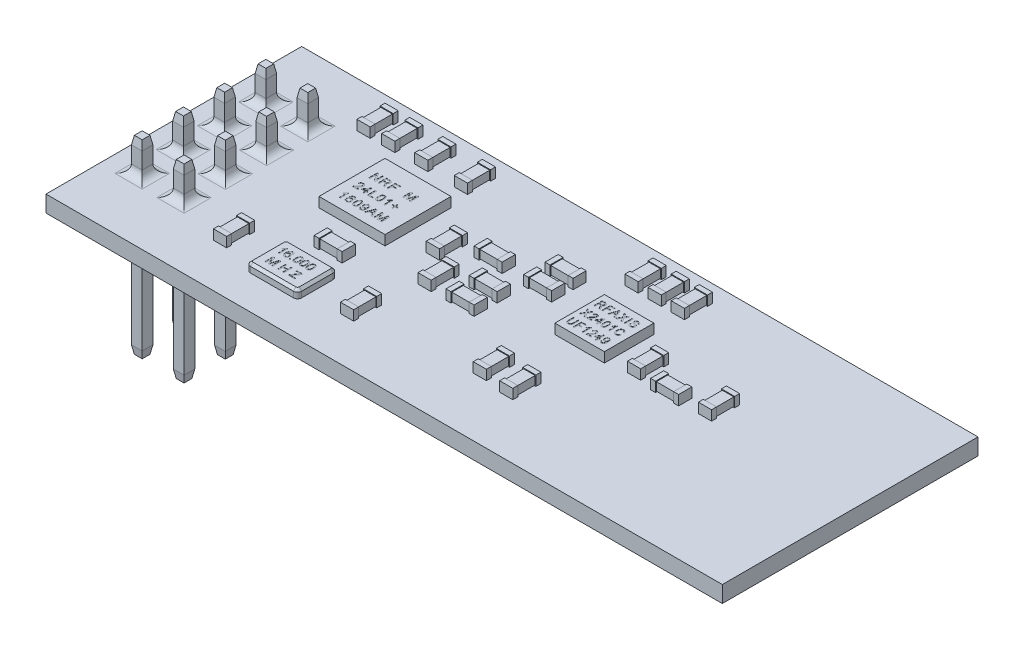
SolidWorks part; units mm, degrees
ref_plane "Спереди" through (0, 0, 0) normal (0, 0, 1) x (1, 0, 0)
ref_plane "Сверху" through (0, 0, 0) normal (0, 1, 0) x (1, 0, 0)
ref_plane "Справа" through (0, 0, 0) normal (1, 0, 0) x (0, 0, -1)
sketch "Эскиз1" plane through (0, 0, 0) normal (0, 1, 0) x (1, 0, 0)
  line L1 (0, -7.75) -> (41, -7.75)
  line L2 (0, -7.75) -> (0, 7.75)
  line L3 (0, 7.75) -> (41, 7.75)
  line L4 (41, -7.75) -> (41, 7.75)
  dimension "D1" = 41
  dimension "D2" = 15.5
extrude "Бобышка-Вытянуть1" add sketch "Эскиз1" along normal blind 1
sketch "Эскиз2" plane through (0, 0, 0) normal (0, -1, 0) x (1, 0, 0)
  line L0 (0, 0) -> (0.6, 0) construction
  line L1 (0, -7.75) -> (0, 7.75) construction
  line L2 (0.6, 4.5) -> (0.6, 3)
  line L3 (0.6, 3) -> (1.1, 2.5)
  line L4 (1.1, 2.5) -> (0.6, 2)
  line L5 (0.6, 2) -> (0.6, 0.5)
  line L6 (0.6, 0.5) -> (1.1, 0)
  line L7 (1.1, 0) -> (0.6, -0.5)
  line L8 (0.6, -0.5) -> (0.6, -2)
  line L9 (0.6, -2) -> (1.1, -2.5)
  line L10 (1.1, -2.5) -> (0.6, -3)
  line L11 (0.6, -3) -> (0.6, -4.5)
  line L12 (0.6, -4.5) -> (1.1, -5)
  line L13 (1.1, -5) -> (5.1, -5)
  line L14 (5.1, -5) -> (5.6, -4.5)
  line L15 (5.6, -4.5) -> (5.6, -3)
  line L16 (5.6, -3) -> (5.1, -2.5)
  line L17 (5.1, -2.5) -> (5.6, -2)
  line L18 (5.6, -2) -> (5.6, -0.5)
  line L19 (5.6, -0.5) -> (5.1, 0)
  line L20 (5.1, 0) -> (5.6, 0.5)
  line L21 (5.6, 0.5) -> (5.6, 2)
  line L22 (5.6, 2) -> (5.1, 2.5)
  line L23 (5.1, 2.5) -> (5.6, 3)
  line L24 (5.6, 3) -> (5.6, 4.5)
  line L25 (5.6, 4.5) -> (5.1, 5)
  line L26 (5.1, 5) -> (1.1, 5)
  line L27 (1.1, 5) -> (0.6, 4.5)
  line L28 (0.6, 0.5) -> (0.6, -0.5) construction
  line L29 (1.1, 2.5) -> (5.1, 2.5) construction
  line L30 (1.1, 0) -> (5.1, 0) construction
  line L31 (1.1, -2.5) -> (5.1, -2.5) construction
  dimension "D1" = 5
  dimension "D2" = 10
  dimension "D3" = 0.5
  dimension "D4" = 0.6
extrude "Бобышка-Вытянуть2" add sketch "Эскиз2" along normal blind 2.5
sketch "Эскиз3" plane through (0, -2.5, 0) normal (0, -1, 0) x (1, 0, 0)
  line L0 (3.1, 5) -> (3.1, -5) construction
  line L1 (5.1, 5) -> (1.1, 5) construction
  line L2 (1.1, -5) -> (5.1, -5) construction
  line L3 (1.83, 3.75) -> (4.37, 3.75) construction
  line L4 (0.6, 3.75) -> (1.83, 3.75) construction
  line L5 (0.6, 4.5) -> (0.6, 3) construction
  line L6 (0.6, 1.25) -> (1.83, 1.25) construction
  line L7 (0.6, 2) -> (0.6, 0.5) construction
  line L8 (1.83, 1.25) -> (4.37, 1.25) construction
  line L9 (4.37, 1.25) -> (4.37, 3.75) construction
  line L10 (1.83, 3.75) -> (1.83, 1.25) construction
  line L11 (0.6, -1.25) -> (1.83, -1.25) construction
  line L12 (0.6, -0.5) -> (0.6, -2) construction
  line L13 (1.83, -1.25) -> (1.83, 1.25) construction
  line L14 (1.83, -1.25) -> (4.37, -1.25) construction
  line L15 (4.37, -1.25) -> (4.37, 1.25) construction
  line L16 (0.6, -3.75) -> (1.83, -3.75) construction
  line L17 (0.6, -3) -> (0.6, -4.5) construction
  line L18 (1.83, -3.75) -> (1.83, -1.25) construction
  line L19 (1.83, -3.75) -> (4.37, -3.75) construction
  line L20 (4.37, -3.75) -> (4.37, -1.25) construction
  line L21 (1.505, 4.075) -> (2.155, 3.425) construction
  line L22 (1.505, 3.425) -> (2.155, 3.425)
  line L23 (1.505, 3.425) -> (1.505, 4.075)
  line L24 (1.505, 4.075) -> (2.155, 4.075)
  line L25 (2.155, 3.425) -> (2.155, 4.075)
  line L26 (4.045, 3.425) -> (4.695, 3.425)
  line L27 (4.045, 3.425) -> (4.045, 4.075)
  line L28 (4.045, 4.075) -> (4.695, 4.075)
  line L29 (4.695, 3.425) -> (4.695, 4.075)
  line L30 (1.505, 0.925) -> (2.155, 0.925)
  line L31 (1.505, 0.925) -> (1.505, 1.575)
  line L32 (1.505, 1.575) -> (2.155, 1.575)
  line L33 (2.155, 0.925) -> (2.155, 1.575)
  line L34 (4.045, 0.925) -> (4.695, 0.925)
  line L35 (4.045, 0.925) -> (4.045, 1.575)
  line L36 (4.045, 1.575) -> (4.695, 1.575)
  line L37 (4.695, 0.925) -> (4.695, 1.575)
  line L38 (1.505, -1.575) -> (2.155, -1.575)
  line L39 (1.505, -1.575) -> (1.505, -0.925)
  line L40 (1.505, -0.925) -> (2.155, -0.925)
  line L41 (2.155, -1.575) -> (2.155, -0.925)
  line L42 (4.045, -1.575) -> (4.695, -1.575)
  line L43 (4.045, -1.575) -> (4.045, -0.925)
  line L44 (4.045, -0.925) -> (4.695, -0.925)
  line L45 (4.695, -1.575) -> (4.695, -0.925)
  line L46 (1.505, -4.075) -> (2.155, -4.075)
  line L47 (1.505, -4.075) -> (1.505, -3.425)
  line L48 (1.505, -3.425) -> (2.155, -3.425)
  line L49 (2.155, -4.075) -> (2.155, -3.425)
  line L50 (4.045, -4.075) -> (4.695, -4.075)
  line L51 (4.045, -4.075) -> (4.045, -3.425)
  line L52 (4.045, -3.425) -> (4.695, -3.425)
  line L53 (4.695, -4.075) -> (4.695, -3.425)
  line L54 (4.045, 4.075) -> (4.695, 3.425) construction
  line L55 (1.505, 1.575) -> (2.155, 0.925) construction
  line L56 (4.045, 1.575) -> (4.695, 0.925) construction
  line L57 (1.505, -0.925) -> (2.155, -1.575) construction
  line L58 (4.045, -0.925) -> (4.695, -1.575) construction
  line L59 (1.505, -3.425) -> (2.155, -4.075) construction
  line L60 (4.045, -3.425) -> (4.695, -4.075) construction
  point P8 (3.1, 3.75)
  dimension "D1" = 2.54
  dimension "D2" = 0.65
extrude "Бобышка-Вытянуть3" add sketch "Эскиз3" along normal blind 6
sketch "Эскиз8" plane through (0, 1, 0) normal (0, 1, 0) x (1, 0, 0)
  line L0 (2.155, -3.425) -> (2.155, -4.075) construction
  line L1 (1.505, 3.425) -> (2.155, 3.425)
  line L2 (1.505, 3.425) -> (1.505, 4.075)
  line L3 (1.505, 4.075) -> (2.155, 4.075)
  line L4 (2.155, 3.425) -> (2.155, 4.075)
  line L5 (4.045, 3.425) -> (4.695, 3.425)
  line L6 (4.045, 3.425) -> (4.045, 4.075)
  line L7 (4.045, 4.075) -> (4.695, 4.075)
  line L8 (4.695, 3.425) -> (4.695, 4.075)
  line L9 (1.505, 0.925) -> (2.155, 0.925)
  line L10 (1.505, 0.925) -> (1.505, 1.575)
  line L11 (1.505, 1.575) -> (2.155, 1.575)
  line L12 (2.155, 0.925) -> (2.155, 1.575)
  line L13 (4.045, 0.925) -> (4.695, 0.925)
  line L14 (4.045, 0.925) -> (4.045, 1.575)
  line L15 (4.045, 1.575) -> (4.695, 1.575)
  line L16 (4.695, 0.925) -> (4.695, 1.575)
  line L17 (1.505, -1.575) -> (2.155, -1.575)
  line L18 (1.505, -1.575) -> (1.505, -0.925)
  line L19 (1.505, -0.925) -> (2.155, -0.925)
  line L20 (2.155, -1.575) -> (2.155, -0.925)
  line L21 (4.045, -1.575) -> (4.695, -1.575)
  line L22 (4.045, -1.575) -> (4.045, -0.925)
  line L23 (4.045, -0.925) -> (4.695, -0.925)
  line L24 (4.695, -1.575) -> (4.695, -0.925)
  line L25 (1.505, -4.075) -> (2.155, -4.075)
  line L26 (1.505, -4.075) -> (1.505, -3.425)
  line L27 (1.505, -3.425) -> (2.155, -3.425)
  line L28 (2.155, -4.075) -> (2.155, -3.425)
  line L30 (4.045, -4.075) -> (4.695, -4.075)
  line L31 (4.045, -4.075) -> (4.045, -3.425)
  line L32 (4.045, -3.425) -> (4.695, -3.425)
  line L33 (4.695, -4.075) -> (4.695, -3.425)
extrude "Бобышка-Вытянуть5" add sketch "Эскиз8" along normal blind 2
chamfer "Фаска1" distance 0.5 angle 10 64 edges at (4.37, -8.5, -4.075) (4.695, -8.5, -3.75) (4.37, -8.5, -3.425) (4.045, -8.5, -3.75) (2.155, -8.5, -3.75) (1.83, -8.5, -4.075) (1.505, -8.5, -3.75) (1.83, -8.5, -3.425) (4.37, -8.5, -1.575) (4.695, -8.5, -1.25) (4.37, -8.5, -0.925) (4.045, -8.5, -1.25) (2.155, -8.5, -1.25) (1.83, -8.5, -1.575) (1.505, -8.5, -1.25) (1.83, -8.5, -0.925) (4.37, -8.5, 0.925) (4.695, -8.5, 1.25) (4.37, -8.5, 1.575) (4.045, -8.5, 1.25) (2.155, -8.5, 1.25) (1.83, -8.5, 0.925) (1.505, -8.5, 1.25) (1.83, -8.5, 1.575) (4.37, -8.5, 3.425) (4.695, -8.5, 3.75) (4.37, -8.5, 4.075) (4.045, -8.5, 3.75) (2.155, -8.5, 3.75) (1.83, -8.5, 4.075) (1.505, -8.5, 3.75) (1.83, -8.5, 3.425) (4.695, 3, -3.75) (4.37, 3, -4.075) (4.045, 3, -3.75) (4.37, 3, -3.425) (2.155, 3, -3.75) (1.83, 3, -4.075) (1.505, 3, -3.75) (1.83, 3, -3.425) (4.695, 3, -1.25) (4.37, 3, -1.575) (4.045, 3, -1.25) (4.37, 3, -0.925) (2.155, 3, -1.25) (1.83, 3, -1.575) (1.505, 3, -1.25) (1.83, 3, -0.925) (4.695, 3, 1.25) (4.37, 3, 0.925) (4.045, 3, 1.25) (4.37, 3, 1.575) (2.155, 3, 1.25) (1.83, 3, 0.925) (1.505, 3, 1.25) (1.83, 3, 1.575) (4.695, 3, 3.75) (4.37, 3, 3.425) (4.045, 3, 3.75) (4.37, 3, 4.075) (2.155, 3, 3.75) (1.83, 3, 3.425) (1.505, 3, 3.75) (1.83, 3, 4.075)
fillet "Скругление1" radius 0.5 32 edges at (1.83, 1, 3.425) (1.505, 1, 3.75) (2.155, 1, 3.75) (1.83, 1, 4.075) (4.695, 1, -3.75) (4.37, 1, -4.075) (4.045, 1, -3.75) (4.37, 1, -3.425) (2.155, 1, -3.75) (1.83, 1, -4.075) (1.505, 1, -3.75) (1.83, 1, -3.425) (4.695, 1, -1.25) (4.37, 1, -1.575) (4.045, 1, -1.25) (4.37, 1, -0.925) (2.155, 1, -1.25) (1.83, 1, -1.575) (1.505, 1, -1.25) (1.83, 1, -0.925) (2.155, 1, 1.25) (1.83, 1, 0.925) (1.505, 1, 1.25) (1.83, 1, 1.575) (4.695, 1, 1.25) (4.37, 1, 0.925) (4.045, 1, 1.25) (4.37, 1, 1.575) (4.695, 1, 3.75) (4.37, 1, 3.425) (4.045, 1, 3.75) (4.37, 1, 4.075)
sketch "Эскиз9" plane through (0, 1, 0) normal (0, 1, 0) x (1, 0, 0)
  line L0 (6.5, 6.4) -> (6.5, 5.3) construction
  line L1 (6.1, 6.4) -> (6.9, 6.4)
  line L2 (6.1, 6.4) -> (6.1, 6.7)
  line L3 (6.1, 6.7) -> (6.9, 6.7)
  line L4 (6.9, 6.4) -> (6.9, 6.7)
  line L5 (7.6, 6.4) -> (8.4, 6.4)
  line L6 (7.6, 6.4) -> (7.6, 6.7)
  line L7 (7.6, 6.7) -> (8.4, 6.7)
  line L8 (8.4, 6.4) -> (8.4, 6.7)
  line L9 (9.6, 6.4) -> (10.4, 6.4)
  line L10 (9.6, 6.4) -> (9.6, 6.7)
  line L11 (9.6, 6.7) -> (10.4, 6.7)
  line L12 (10.4, 6.4) -> (10.4, 6.7)
  line L13 (12, 6.4) -> (12.8, 6.4)
  line L14 (12, 6.4) -> (12, 6.7)
  line L15 (12, 6.7) -> (12.8, 6.7)
  line L16 (12.8, 6.4) -> (12.8, 6.7)
  line L17 (8, 6.4) -> (8, 5.3) construction
  line L18 (10, 6.4) -> (10, 5.3) construction
  line L19 (12.4, 6.4) -> (12.4, 5.3) construction
  line L20 (7.9, -3.7) -> (7.9, -4.8) construction
  line L21 (6.1, 5) -> (6.9, 5)
  line L22 (6.1, 5) -> (6.1, 5.3)
  line L23 (6.1, 5.3) -> (6.9, 5.3)
  line L24 (6.9, 5) -> (6.9, 5.3)
  line L25 (7.6, 5) -> (8.4, 5)
  line L26 (7.6, 5) -> (7.6, 5.3)
  line L27 (7.6, 5.3) -> (8.4, 5.3)
  line L28 (8.4, 5) -> (8.4, 5.3)
  line L29 (9.6, 5) -> (10.4, 5)
  line L30 (9.6, 5) -> (9.6, 5.3)
  line L31 (9.6, 5.3) -> (10.4, 5.3)
  line L32 (10.4, 5) -> (10.4, 5.3)
  line L33 (12, 5) -> (12.8, 5)
  line L34 (12, 5) -> (12, 5.3)
  line L35 (12, 5.3) -> (12.8, 5.3)
  line L36 (12.8, 5) -> (12.8, 5.3)
  line L37 (7.5, -3.7) -> (8.3, -3.7)
  line L38 (7.5, -3.7) -> (7.5, -3.4)
  line L39 (7.5, -3.4) -> (8.3, -3.4)
  line L40 (8.3, -3.7) -> (8.3, -3.4)
  line L41 (7.5, -5.1) -> (8.3, -5.1)
  line L42 (7.5, -5.1) -> (7.5, -4.8)
  line L43 (7.5, -4.8) -> (8.3, -4.8)
  line L44 (8.3, -5.1) -> (8.3, -4.8)
  line L45 (22.75, 6.4) -> (22.75, 5.3) construction
  line L46 (22.35, 6.7) -> (23.15, 6.7)
  line L47 (22.35, 6.7) -> (22.35, 6.4)
  line L48 (22.35, 6.4) -> (23.15, 6.4)
  line L49 (23.15, 6.7) -> (23.15, 6.4)
  line L50 (23.75, 6.7) -> (24.55, 6.7)
  line L51 (23.75, 6.7) -> (23.75, 6.4)
  line L52 (23.75, 6.4) -> (24.55, 6.4)
  line L53 (24.55, 6.7) -> (24.55, 6.4)
  line L54 (25.15, 6.7) -> (25.95, 6.7)
  line L55 (25.15, 6.7) -> (25.15, 6.4)
  line L56 (25.15, 6.4) -> (25.95, 6.4)
  line L57 (25.95, 6.7) -> (25.95, 6.4)
  line L58 (22.35, 5) -> (23.15, 5)
  line L59 (22.35, 5) -> (22.35, 5.3)
  line L60 (22.35, 5.3) -> (23.15, 5.3)
  line L61 (23.15, 5) -> (23.15, 5.3)
  line L62 (23.75, 5) -> (24.55, 5)
  line L63 (23.75, 5) -> (23.75, 5.3)
  line L64 (23.75, 5.3) -> (24.55, 5.3)
  line L65 (24.55, 5) -> (24.55, 5.3)
  line L66 (25.15, 5) -> (25.95, 5)
  line L67 (25.15, 5) -> (25.15, 5.3)
  line L68 (25.15, 5.3) -> (25.95, 5.3)
  line L69 (25.95, 5) -> (25.95, 5.3)
  line L70 (24.15, 6.4) -> (24.15, 5.3) construction
  line L71 (25.55, 6.4) -> (25.55, 5.3) construction
  line L72 (11.2, -2) -> (12.3, -2) construction
  line L73 (10.9, -2.4) -> (11.2, -2.4)
  line L74 (10.9, -2.4) -> (10.9, -1.6)
  line L75 (10.9, -1.6) -> (11.2, -1.6)
  line L76 (11.2, -2.4) -> (11.2, -1.6)
  line L77 (12.3, -2.4) -> (12.6, -2.4)
  line L78 (12.3, -2.4) -> (12.3, -1.6)
  line L79 (12.3, -1.6) -> (12.6, -1.6)
  line L80 (12.6, -2.4) -> (12.6, -1.6)
  line L81 (15.6, -3.7) -> (15.6, -4.8) construction
  line L82 (15.2, -3.4) -> (16, -3.4)
  line L83 (15.2, -3.4) -> (15.2, -3.7)
  line L84 (15.2, -3.7) -> (16, -3.7)
  line L85 (16, -3.4) -> (16, -3.7)
  line L86 (15.2, -5.1) -> (16, -5.1)
  line L87 (15.2, -5.1) -> (15.2, -4.8)
  line L88 (15.2, -4.8) -> (16, -4.8)
  line L89 (16, -5.1) -> (16, -4.8)
  line L90 (27.4, 1.9) -> (27.4, 0.8) construction
  line L91 (27, 1.9) -> (27.8, 1.9)
  line L92 (27, 1.9) -> (27, 2.2)
  line L93 (27, 2.2) -> (27.8, 2.2)
  line L94 (27.8, 1.9) -> (27.8, 2.2)
  line L95 (27, 0.5) -> (27.8, 0.5)
  line L96 (27, 0.5) -> (27, 0.8)
  line L97 (27, 0.8) -> (27.8, 0.8)
  line L98 (27.8, 0.5) -> (27.8, 0.8)
  line L99 (31.7, 1.9) -> (31.7, 0.8) construction
  line L100 (31.3, 2.2) -> (32.1, 2.2)
  line L101 (31.3, 2.2) -> (31.3, 1.9)
  line L102 (31.3, 1.9) -> (32.1, 1.9)
  line L103 (32.1, 2.2) -> (32.1, 1.9)
  line L104 (31.3, 0.5) -> (32.1, 0.5)
  line L105 (31.3, 0.5) -> (31.3, 0.8)
  line L106 (31.3, 0.8) -> (32.1, 0.8)
  line L107 (32.1, 0.5) -> (32.1, 0.8)
  line L108 (28.9, 0.7) -> (30, 0.7) construction
  line L109 (28.6, 0.3) -> (28.9, 0.3)
  line L110 (28.6, 0.3) -> (28.6, 1.1)
  line L111 (28.6, 1.1) -> (28.9, 1.1)
  line L112 (28.9, 0.3) -> (28.9, 1.1)
  line L113 (30, 0.3) -> (30.3, 0.3)
  line L114 (30, 0.3) -> (30, 1.1)
  line L115 (30, 1.1) -> (30.3, 1.1)
  line L116 (30.3, 0.3) -> (30.3, 1.1)
  line L117 (22.75, -2.8) -> (22.75, -3.9) construction
  line L118 (22.35, -2.8) -> (23.15, -2.8)
  line L119 (22.35, -2.8) -> (22.35, -2.5)
  line L120 (22.35, -2.5) -> (23.15, -2.5)
  line L121 (23.15, -2.8) -> (23.15, -2.5)
  line L122 (22.35, -4.2) -> (23.15, -4.2)
  line L123 (22.35, -4.2) -> (22.35, -3.9)
  line L124 (22.35, -3.9) -> (23.15, -3.9)
  line L125 (23.15, -4.2) -> (23.15, -3.9)
  line L126 (24.55, -3) -> (24.55, -4.1) construction
  line L127 (24.15, -3) -> (24.95, -3)
  line L128 (24.15, -3) -> (24.15, -2.7)
  line L129 (24.15, -2.7) -> (24.95, -2.7)
  line L130 (24.95, -3) -> (24.95, -2.7)
  line L131 (24.15, -4.4) -> (24.95, -4.4)
  line L132 (24.15, -4.4) -> (24.15, -4.1)
  line L133 (24.15, -4.1) -> (24.95, -4.1)
  line L134 (24.95, -4.4) -> (24.95, -4.1)
  line L135 (16.4, 0.2) -> (16.4, -0.9) construction
  line L136 (16, -1.2) -> (16.8, -1.2)
  line L137 (16, -1.2) -> (16, -0.9)
  line L138 (16, -0.9) -> (16.8, -0.9)
  line L139 (16.8, -1.2) -> (16.8, -0.9)
  line L140 (16, 0.2) -> (16.8, 0.2)
  line L141 (16, 0.2) -> (16, 0.5)
  line L142 (16, 0.5) -> (16.8, 0.5)
  line L143 (16.8, 0.2) -> (16.8, 0.5)
  line L144 (15, 2.1) -> (15, 1) construction
  line L145 (14.6, 0.7) -> (15.4, 0.7)
  line L146 (14.6, 0.7) -> (14.6, 1)
  line L147 (14.6, 1) -> (15.4, 1)
  line L148 (15.4, 0.7) -> (15.4, 1)
  line L149 (14.6, 2.1) -> (15.4, 2.1)
  line L150 (14.6, 2.1) -> (14.6, 2.4)
  line L151 (14.6, 2.4) -> (15.4, 2.4)
  line L152 (15.4, 2.1) -> (15.4, 2.4)
  line L153 (16.6, 2.3) -> (17.7, 2.3) construction
  line L154 (16.3, 1.9) -> (16.6, 1.9)
  line L155 (16.3, 1.9) -> (16.3, 2.7)
  line L156 (16.3, 2.7) -> (16.6, 2.7)
  line L157 (16.6, 1.9) -> (16.6, 2.7)
  line L158 (17.7, 1.9) -> (18, 1.9)
  line L159 (17.7, 1.9) -> (17.7, 2.7)
  line L160 (17.7, 2.7) -> (18, 2.7)
  line L161 (18, 1.9) -> (18, 2.7)
  line L162 (19.3, 1.9) -> (19.6, 1.9)
  line L163 (19.3, 1.9) -> (19.3, 2.7)
  line L164 (19.3, 2.7) -> (19.6, 2.7)
  line L165 (19.6, 1.9) -> (19.6, 2.7)
  line L166 (20.7, 1.9) -> (21, 1.9)
  line L167 (20.7, 1.9) -> (20.7, 2.7)
  line L168 (20.7, 2.7) -> (21, 2.7)
  line L169 (21, 1.9) -> (21, 2.7)
  line L170 (19.3, 3.2) -> (19.6, 3.2)
  line L171 (19.3, 3.2) -> (19.3, 4)
  line L172 (19.3, 4) -> (19.6, 4)
  line L173 (19.6, 3.2) -> (19.6, 4)
  line L174 (20.7, 3.2) -> (21, 3.2)
  line L175 (20.7, 3.2) -> (20.7, 4)
  line L176 (20.7, 4) -> (21, 4)
  line L177 (21, 3.2) -> (21, 4)
  line L178 (19.6, 2.3) -> (20.7, 2.3) construction
  line L179 (19.6, 3.6) -> (20.7, 3.6) construction
  line L180 (18, 0.6) -> (19.1, 0.6) construction
  line L181 (17.7, -1.2) -> (18, -1.2)
  line L182 (17.7, -1.2) -> (17.7, -0.4)
  line L183 (17.7, -0.4) -> (18, -0.4)
  line L184 (18, -1.2) -> (18, -0.4)
  line L185 (19.1, -1.2) -> (19.4, -1.2)
  line L186 (19.1, -1.2) -> (19.1, -0.4)
  line L187 (19.1, -0.4) -> (19.4, -0.4)
  line L188 (19.4, -1.2) -> (19.4, -0.4)
  line L189 (17.7, 0.2) -> (18, 0.2)
  line L190 (17.7, 0.2) -> (17.7, 1)
  line L191 (17.7, 1) -> (18, 1)
  line L192 (18, 0.2) -> (18, 1)
  line L193 (19.1, 0.2) -> (19.4, 0.2)
  line L194 (19.1, 0.2) -> (19.1, 1)
  line L195 (19.1, 1) -> (19.4, 1)
  line L196 (19.4, 0.2) -> (19.4, 1)
  line L197 (18, -0.8) -> (19.1, -0.8) construction
  dimension "D1" = 1.7
  dimension "D2" = 0.8
  dimension "D3" = 6.5
  dimension "D4" = 5
  dimension "D5" = 0.3
  dimension "D6" = 1.5
  dimension "D7" = 2
  dimension "D8" = 2.4
  dimension "D9" = 0.8
  dimension "D10" = 1.7
  dimension "D11" = 0.3
  dimension "D12" = 3.4
  dimension "D13" = 7.9
  dimension "D14" = 10.35
  dimension "D15" = 1.4
  dimension "D16" = 1.4
  dimension "D17" = 1.7
  dimension "D18" = 0.8
  dimension "D19" = 0.3
  dimension "D20" = 2
  dimension "D21" = 10.9
  dimension "D22" = 7.7
  dimension "D23" = 1.7
  dimension "D24" = 0.8
  dimension "D25" = 0.3
  dimension "D26" = 27.4
  dimension "D27" = 0.5
  dimension "D28" = 4.3
  dimension "D29" = 1.7
  dimension "D30" = 1.2
  dimension "D31" = 0.3
  dimension "D32" = 1.5
  dimension "D33" = 1.7
  dimension "D34" = 0.8
  dimension "D35" = 0.3
  dimension "D36" = 7.15
  dimension "D37" = 2.5
  dimension "D38" = 1.8
  dimension "D39" = 0.2
  dimension "D40" = 0.8
  dimension "D41" = 1.7
  dimension "D42" = 0.3
  dimension "D43" = 1.2
  dimension "D44" = 16.4
  dimension "D45" = 1.4
  dimension "D46" = 0.2
  dimension "D47" = 1.8
  dimension "D48" = 1.3
  dimension "D49" = 1.3
  dimension "D50" = 1.3
  dimension "D51" = 1.3
  dimension "D52" = 1.4
  dimension "D53" = 0.4
extrude "Бобышка-Вытянуть6" add sketch "Эскиз9" along normal blind 0.6
sketch "Эскиз10" plane through (0, 1, 0) normal (0, 1, 0) x (1, 0, 0)
  line L0 (6.1, 6.4) -> (6.9, 6.4) construction
  line L1 (7.6, 6.4) -> (8.4, 6.4) construction
  line L2 (9.6, 6.4) -> (10.4, 6.4) construction
  line L3 (12, 6.4) -> (12.8, 6.4) construction
  line L4 (6.9, 5.3) -> (6.1, 5.3) construction
  line L5 (6.15, 5.3) -> (6.85, 5.3)
  line L6 (6.15, 5.3) -> (6.15, 6.4)
  line L7 (6.15, 6.4) -> (6.85, 6.4)
  line L8 (6.85, 5.3) -> (6.85, 6.4)
  line L9 (8.4, 5.3) -> (7.6, 5.3) construction
  line L10 (7.65, 5.3) -> (8.35, 5.3)
  line L11 (7.65, 5.3) -> (7.65, 6.4)
  line L12 (7.65, 6.4) -> (8.35, 6.4)
  line L13 (8.35, 5.3) -> (8.35, 6.4)
  line L14 (10.4, 5.3) -> (9.6, 5.3) construction
  line L15 (9.65, 5.3) -> (10.35, 5.3)
  line L16 (9.65, 5.3) -> (9.65, 6.4)
  line L17 (9.65, 6.4) -> (10.35, 6.4)
  line L18 (10.35, 5.3) -> (10.35, 6.4)
  line L19 (12.8, 5.3) -> (12, 5.3) construction
  line L20 (12.05, 5.3) -> (12.75, 5.3)
  line L21 (12.05, 5.3) -> (12.05, 6.4)
  line L22 (12.05, 6.4) -> (12.75, 6.4)
  line L23 (12.75, 5.3) -> (12.75, 6.4)
  line L24 (7.5, -3.7) -> (8.3, -3.7) construction
  line L25 (22.35, 6.4) -> (23.15, 6.4) construction
  line L26 (23.75, 6.4) -> (24.55, 6.4) construction
  line L27 (25.15, 6.4) -> (25.95, 6.4) construction
  line L28 (8.3, -4.8) -> (7.5, -4.8) construction
  line L29 (7.55, -4.8) -> (8.25, -4.8)
  line L30 (7.55, -4.8) -> (7.55, -3.7)
  line L31 (7.55, -3.7) -> (8.25, -3.7)
  line L32 (8.25, -4.8) -> (8.25, -3.7)
  line L33 (23.15, 5.3) -> (22.35, 5.3) construction
  line L34 (22.4, 5.3) -> (23.1, 5.3)
  line L35 (22.4, 5.3) -> (22.4, 6.4)
  line L36 (22.4, 6.4) -> (23.1, 6.4)
  line L37 (23.1, 5.3) -> (23.1, 6.4)
  line L38 (24.55, 5.3) -> (23.75, 5.3) construction
  line L39 (23.8, 5.3) -> (24.5, 5.3)
  line L40 (23.8, 5.3) -> (23.8, 6.4)
  line L41 (23.8, 6.4) -> (24.5, 6.4)
  line L42 (24.5, 5.3) -> (24.5, 6.4)
  line L43 (23.75, 6.4) -> (24.55, 6.4) construction
  line L44 (25.95, 5.3) -> (25.15, 5.3) construction
  line L45 (25.2, 5.3) -> (25.9, 5.3)
  line L46 (25.2, 5.3) -> (25.2, 6.4)
  line L47 (25.2, 6.4) -> (25.9, 6.4)
  line L48 (25.9, 5.3) -> (25.9, 6.4)
  line L49 (25.15, 6.4) -> (25.95, 6.4) construction
  line L50 (11.2, -2.4) -> (11.2, -1.6) construction
  line L51 (12.3, -1.6) -> (12.3, -2.4) construction
  line L52 (11.2, -2.35) -> (12.3, -2.35)
  line L53 (11.2, -2.35) -> (11.2, -1.65)
  line L54 (11.2, -1.65) -> (12.3, -1.65)
  line L55 (12.3, -2.35) -> (12.3, -1.65)
  line L56 (15.2, -3.7) -> (16, -3.7) construction
  line L57 (16, -4.8) -> (15.2, -4.8) construction
  line L58 (15.25, -4.8) -> (15.95, -4.8)
  line L59 (15.25, -4.8) -> (15.25, -3.7)
  line L60 (15.25, -3.7) -> (15.95, -3.7)
  line L61 (15.95, -4.8) -> (15.95, -3.7)
  line L62 (15.2, -3.7) -> (16, -3.7) construction
  line L63 (27, 1.9) -> (27.8, 1.9) construction
  line L64 (27.8, 0.8) -> (27, 0.8) construction
  line L65 (27.05, 0.8) -> (27.75, 0.8)
  line L66 (27.05, 0.8) -> (27.05, 1.9)
  line L67 (27.05, 1.9) -> (27.75, 1.9)
  line L68 (27.75, 0.8) -> (27.75, 1.9)
  line L69 (27, 1.9) -> (27.8, 1.9) construction
  line L70 (31.3, 1.9) -> (32.1, 1.9) construction
  line L71 (32.1, 0.8) -> (31.3, 0.8) construction
  line L72 (31.35, 0.8) -> (32.05, 0.8)
  line L73 (31.35, 0.8) -> (31.35, 1.9)
  line L74 (31.35, 1.9) -> (32.05, 1.9)
  line L75 (32.05, 0.8) -> (32.05, 1.9)
  line L76 (28.9, 0.3) -> (28.9, 1.1) construction
  line L77 (28.9, 0.3) -> (28.9, 1.1) construction
  line L78 (28.9, 0.35) -> (30, 0.35)
  line L79 (28.9, 0.35) -> (28.9, 1.05)
  line L80 (28.9, 1.05) -> (30, 1.05)
  line L81 (30, 0.35) -> (30, 1.05)
  line L82 (30, 1.1) -> (30, 0.3) construction
  line L83 (22.35, -2.8) -> (23.15, -2.8) construction
  line L84 (24.15, -3) -> (24.95, -3) construction
  line L85 (23.15, -3.9) -> (22.35, -3.9) construction
  line L86 (22.4, -3.9) -> (23.1, -3.9)
  line L87 (22.4, -3.9) -> (22.4, -2.8)
  line L88 (22.4, -2.8) -> (23.1, -2.8)
  line L89 (23.1, -3.9) -> (23.1, -2.8)
  line L90 (24.95, -4.1) -> (24.15, -4.1) construction
  line L91 (24.2, -4.1) -> (24.9, -4.1)
  line L92 (24.2, -4.1) -> (24.2, -3)
  line L93 (24.2, -3) -> (24.9, -3)
  line L94 (24.9, -4.1) -> (24.9, -3)
  line L95 (16, 0.2) -> (16.8, 0.2) construction
  line L96 (16.8, -0.9) -> (16, -0.9) construction
  line L97 (16.05, -0.9) -> (16.75, -0.9)
  line L98 (16.05, -0.9) -> (16.05, 0.2)
  line L99 (16.05, 0.2) -> (16.75, 0.2)
  line L100 (16.75, -0.9) -> (16.75, 0.2)
  line L101 (14.6, 2.1) -> (15.4, 2.1) construction
  line L102 (15.4, 1) -> (14.6, 1) construction
  line L103 (14.65, 1) -> (15.35, 1)
  line L104 (14.65, 1) -> (14.65, 2.1)
  line L105 (14.65, 2.1) -> (15.35, 2.1)
  line L106 (15.35, 1) -> (15.35, 2.1)
  line L107 (14.6, 2.1) -> (15.4, 2.1) construction
  line L108 (16.6, 1.9) -> (16.6, 2.7) construction
  line L109 (19.6, 3.2) -> (19.6, 4) construction
  line L110 (19.6, 1.9) -> (19.6, 2.7) construction
  line L111 (17.7, 2.7) -> (17.7, 1.9) construction
  line L112 (16.6, 1.95) -> (17.7, 1.95)
  line L113 (16.6, 1.95) -> (16.6, 2.65)
  line L114 (16.6, 2.65) -> (17.7, 2.65)
  line L115 (17.7, 1.95) -> (17.7, 2.65)
  line L116 (20.7, 2.7) -> (20.7, 1.9) construction
  line L117 (19.6, 1.95) -> (20.7, 1.95)
  line L118 (19.6, 1.95) -> (19.6, 2.65)
  line L119 (19.6, 2.65) -> (20.7, 2.65)
  line L120 (20.7, 1.95) -> (20.7, 2.65)
  line L121 (20.7, 4) -> (20.7, 3.2) construction
  line L122 (19.6, 3.25) -> (20.7, 3.25)
  line L123 (19.6, 3.25) -> (19.6, 3.95)
  line L124 (19.6, 3.95) -> (20.7, 3.95)
  line L125 (20.7, 3.25) -> (20.7, 3.95)
  line L126 (18, -1.2) -> (18, -0.4) construction
  line L127 (18, 0.2) -> (18, 1) construction
  line L128 (19.1, -0.4) -> (19.1, -1.2) construction
  line L129 (18, -1.15) -> (19.1, -1.15)
  line L130 (18, -1.15) -> (18, -0.45)
  line L131 (18, -0.45) -> (19.1, -0.45)
  line L132 (19.1, -1.15) -> (19.1, -0.45)
  line L133 (19.1, 1) -> (19.1, 0.2) construction
  line L134 (18, 0.25) -> (19.1, 0.25)
  line L135 (18, 0.25) -> (18, 0.95)
  line L136 (18, 0.95) -> (19.1, 0.95)
  line L137 (19.1, 0.25) -> (19.1, 0.95)
  point P0 (6.5, 6.4)
  point P1 (8, 6.4)
  point P4 (10, 6.4)
  point P7 (12.4, 6.4)
  point P36 (22.75, 6.4)
  point P37 (7.9, -3.7)
  point P38 (24.15, 6.4)
  point P43 (25.55, 6.4)
  point P77 (11.2, -2)
  point P85 (15.6, -3.7)
  point P97 (27.4, 1.9)
  point P107 (31.7, 1.9)
  point P116 (28.9, 0.7)
  point P127 (22.75, -2.8)
  point P128 (24.55, -3)
  point P147 (16.4, 0.2)
  point P155 (15, 2.1)
  point P165 (19.6, 3.6)
  point P166 (16.6, 2.3)
  point P167 (19.6, 2.3)
  point P192 (18, 0.6)
  point P195 (18, -0.8)
  dimension "D1" = 0.7
extrude "Бобышка-Вытянуть7" add sketch "Эскиз10" along normal blind 0.5 from offset 0.05
sketch "Эскиз12" plane through (0, 1, 0) normal (0, 1, 0) x (1, 0, 0)
  line L0 (9, 1.8) -> (13, 1.8) construction
  line L1 (9, -0.2) -> (13, -0.2)
  line L2 (9, -0.2) -> (9, 3.8)
  line L3 (9, 3.8) -> (13, 3.8)
  line L4 (13, -0.2) -> (13, 3.8)
  line L5 (22.8, 1.8) -> (25.8, 1.8) construction
  line L6 (22.8, 0.3) -> (25.8, 0.3)
  line L7 (22.8, 0.3) -> (22.8, 3.3)
  line L8 (22.8, 3.3) -> (25.8, 3.3)
  line L9 (25.8, 0.3) -> (25.8, 3.3)
  dimension "D1" = 4
  dimension "D2" = 4
  dimension "D3" = 9
  dimension "D4" = 0.2
  dimension "D5" = 3
  dimension "D6" = 0.3
  dimension "D7" = 22.8
extrude "Бобышка-Вытянуть9" add sketch "Эскиз12" along normal blind 0.6
sketch "Эскиз13" plane through (0, 1.6, 0) normal (0, 1, 0) x (1, 0, 0)
  line L0 (9, 2.3) -> (12.1601, 2.3) construction
  line L1 (9, 3.8) -> (9, -0.2) construction
  text T0 "  NRF  M\r\n  24L01+\r\n  1609AM" font "Arial" height 0.5
  dimension "D1" = 1.5
extrude "Вырез-Вытянуть2" cut sketch "Эскиз13" against normal blind 0.01
sketch "Эскиз15" plane through (0, 1.6, 0) normal (0, 1, 0) x (1, 0, 0)
  line L0 (22.8, 2.4) -> (25.8, 2.4) construction
  line L1 (22.8, 3.3) -> (22.8, 0.3) construction
  line L2 (25.8, 0.3) -> (25.8, 3.3) construction
  text T0 " RFAXIS\r\n X2401C\r\n UF1249" font "Arial" height 0.5
  dimension "D1" = 0.9
extrude "Вырез-Вытянуть4" cut sketch "Эскиз15" against normal blind 0.01
sketch "Эскиз17" plane through (0, 1, 0) normal (0, 1, 0) x (1, 0, 0)
  line L0 (11.65, -3.3) -> (11.65, -5.7) construction
  line L1 (10.35, -5.7) -> (12.95, -5.7)
  line L2 (10.1, -5.45) -> (10.1, -3.55)
  line L3 (10.35, -3.3) -> (12.95, -3.3)
  line L4 (13.2, -5.45) -> (13.2, -3.55)
  arc A0 (10.35, -5.7) -> (10.1, -5.45) centre (10.35, -5.45) cw
  arc A1 (12.95, -5.7) -> (13.2, -5.45) centre (12.95, -5.45) ccw
  arc A2 (12.95, -3.3) -> (13.2, -3.55) centre (12.95, -3.55) cw
  arc A3 (10.1, -3.55) -> (10.35, -3.3) centre (10.35, -3.55) cw
  dimension "D1" = 0.25
  dimension "D2" = 3.1
  dimension "D3" = 2.4
  dimension "D4" = 10.1
  dimension "D5" = 5.7
extrude "Бобышка-Вытянуть10" add sketch "Эскиз17" along normal blind 0.5
chamfer "Фаска3" distance 0.15 angle 45 8 edges at (11.65, 1.5, 3.3) (10.1732, 1.5, 3.3732) (13.1268, 1.5, 3.3732) (10.1, 1.5, 4.5) (13.2, 1.5, 4.5) (10.1732, 1.5, 5.6268) (13.1268, 1.5, 5.6268) (11.65, 1.5, 5.7)
sketch "Эскиз18" plane through (0, 1.5, 0) normal (0, 1, 0) x (1, 0, 0)
  line L0 (10.25, -4.3) -> (13.05, -4.3) construction
  line L1 (10.25, -3.55) -> (10.25, -5.45) construction
  line L2 (13.05, -5.45) -> (13.05, -3.55) construction
  line L3 (12.95, -3.45) -> (10.35, -3.45) construction
  text T0 " 16.000\r\n  M H Z" font "Arial" height 0.5
  dimension "D1" = 0.85
extrude "Вырез-Вытянуть5" cut sketch "Эскиз18" against normal blind 0.01
